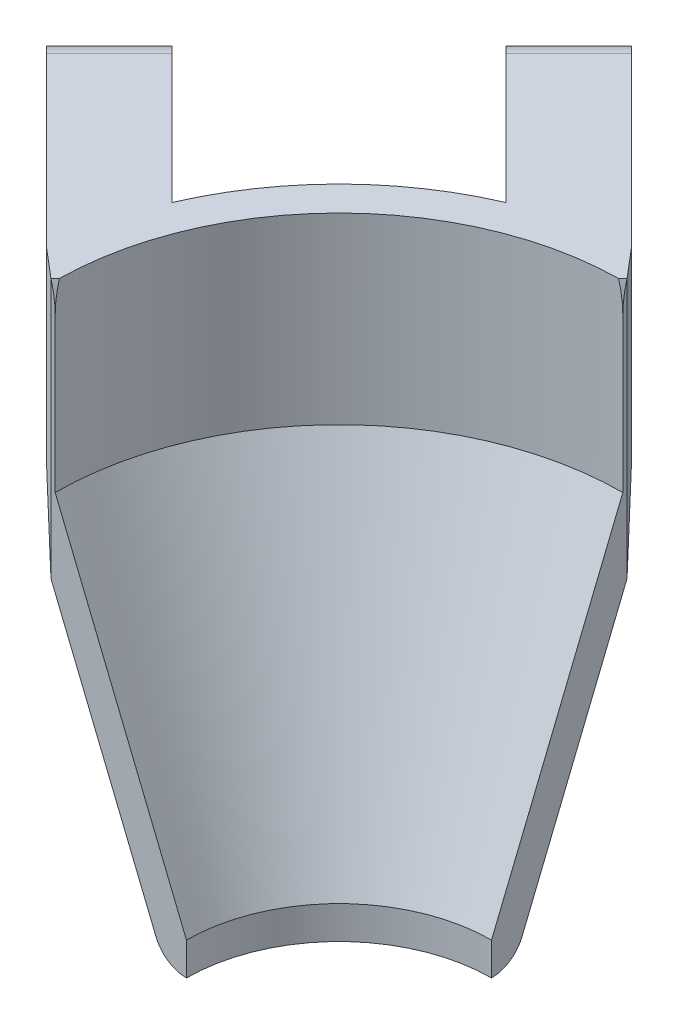
SolidWorks part; units mm, degrees
ref_plane "Alzado" through (0, 0, 0) normal (0, 0, 1) x (1, 0, 0)
ref_plane "Planta" through (0, 0, 0) normal (0, 1, 0) x (1, 0, 0)
ref_plane "Vista lateral" through (0, 0, 0) normal (1, 0, 0) x (0, 0, -1)
sketch "Croquis2" plane through (0, 0, 0) normal (1, 0, 0) x (0, 0, -1)
  line L0 (-25.7956, 35.8166) -> (-40.3139, 90) construction
  line L1 (-40.3139, 90) -> (-34.1023, 90) construction
  line L2 (-34.1023, 90) -> (-20, 37.3696) construction
  line L3 (0, 7.3696) -> (0, 0) construction
  line L4 (0, 0) -> (0, 65.5249) construction
  line L5 (34.1023, 90) -> (20, 37.3696) construction
  line L6 (40.3139, 90) -> (34.1023, 90) construction
  line L7 (25.7956, 35.8166) -> (40.3139, 90) construction
  arc A0 (0, 0) -> (-25.7956, 35.8166) centre (34.3409, 51.9302) cw construction
  arc A1 (-20, 37.3696) -> (0, 7.3696) centre (34.3409, 51.9302) ccw construction
  arc A2 (20, 37.3696) -> (0, 7.3696) centre (-34.3409, 51.9302) cw construction
  arc A3 (0, 0) -> (25.7956, 35.8166) centre (-34.3409, 51.9302) ccw construction
  dimension "D4" = 62.2578
  dimension "D5" = 90
  dimension "D1" = 15
  dimension "D2" = 20
  dimension "D3" = 6
sketch "Croquis3" plane through (0, 0, 0) normal (1, 0, 0) x (0, 0, -1)
  line L0 (25.7956, 0) -> (25.7956, 5.5557)
  line L1 (25.7956, 5.5557) -> (48, 60)
  line L2 (48, 60) -> (48, 91)
  line L3 (48, 91) -> (54, 91)
  line L4 (54, 91) -> (54, 60)
  line L5 (54, 60) -> (30.9399, 3.4577)
  line L6 (0, 0) -> (25.7956, 0) construction
  line L7 (25.7956, 0) -> (25.7956, 35.8166) construction
  line L8 (0, 0) -> (0, 65.5249) construction
  arc A0 (30.9399, 3.4577) -> (25.7956, 0) centre (25.7956, 5.5557) cw
  dimension "D1" = 48
  dimension "D2" = 6
  dimension "D3" = 91
  dimension "D4" = 60
revolve "Revolución1" add sketch "Croquis3" angle 90 about L4
sketch "Croquis4" plane through (0, 91, 0) normal (0, 1, 0) x (1, 0, 0)
  line L0 (0, 0) -> (-47.2208, 47.2208) construction
  line L1 (-85.5599, 36.0624) -> (-74.9533, 46.669)
  line L2 (-74.9533, 46.669) -> (-49.6104, 21.3262)
  line L3 (-53.8262, 4.3287) -> (-85.5599, 36.0624)
  line L4 (0, 0) -> (0, 25.7956) construction
  line L5 (-46.669, 74.9533) -> (-21.3262, 49.6104)
  line L6 (-36.0624, 85.5599) -> (-46.669, 74.9533)
  line L7 (-4.3287, 53.8262) -> (-36.0624, 85.5599)
  line L8 (-38.1838, 38.1838) -> (-66.0102, 10.3574) construction
  arc A0 (0, 54) -> (-54, 0) centre (0, 0) ccw construction
  arc A1 (-49.6104, 21.3262) -> (-53.8262, 4.3287) centre (0, 0) ccw
  arc A2 (-21.3262, 49.6104) -> (-4.3287, 53.8262) centre (0, 0) cw
  dimension "D1" = 45
  dimension "D2" = 15
  dimension "D3" = 20
  dimension "D4" = 32
extrude "Saliente-Extruir1" add sketch "Croquis4" against normal blind 10
fillet "Redondeo1" radius 6 2 edges at (-12.9995, 81, -52.412) (-52.412, 81, -12.9995)
sketch "Croquis5" plane through (-24.7487, 0, 24.7487) normal (-0.7071, 0, 0.7071) x (0.7071, 0, 0.7071)
  line L0 (-86, 81) -> (-86, 91) construction
  circle A0 centre (-59, 86) radius 3
  circle A1 centre (-78, 86) radius 3
  point P11 (-86, 86)
  dimension "D2" = 6
  dimension "D1" = 59
  dimension "D3" = 8
extrude "Cortar-Extruir1" cut sketch "Croquis5" against normal through all
fillet "Redondeo2" radius 5 4 edges at (-80.2566, 81, -41.3657) (-41.3657, 81, -80.2566) (-80.2566, 91, -41.3657) (-41.3657, 91, -80.2566)
ref_axis "Eje1" through (-7.3446, 86, -76.094) along (-0.7071, 0, 0.7071)
sketch "Croquis9" plane through (0, 91, 0) normal (0, 1, 0) x (1, 0, 0)
  line L0 (0, 0) -> (-41.7193, 41.7193) construction
  line L1 (-7.3446, 76.094) -> (-84.0335, -0.5949) construction
  line L2 (-53.8262, 4.3287) -> (-66.468, 16.9706) construction
  line L3 (-82.0244, 32.5269) -> (-53.8262, 4.3287) construction
  dimension "D1" = 59
  dimension "D2" = 17.8782
ref_plane "Plano2" through (27, 0, -27) normal (0.7071, 0, -0.7071) x (-0.7071, 0, -0.7071)
sketch "Croquis14" plane through (27, 0, -27) normal (0.7071, 0, -0.7071) x (-0.7071, 0, -0.7071)
  line L0 (59, 86) -> (33.9411, 86) construction
  line L1 (33.9411, 91) -> (33.9411, 60) construction
  line L2 (0, 91) -> (59, 91) construction
  line L3 (34.445, 91) -> (33.9411, 91)
  line L4 (33.9411, 91) -> (33.9411, 86)
  arc A0 (33.9411, 86) -> (34.445, 91) centre (59, 86) cw
extrude "Cortar-Extruir3" cut sketch "Croquis14" against normal through all
sketch "Croquis17" plane through (0, 91, 0) normal (0, 1, 0) x (1, 0, 0)
  line L0 (-4.3287, 53.8262) -> (0, 48.7126)
  line L1 (0, 48.7126) -> (0, 54)
  line L2 (39.0562, 14.9438) -> (14.9438, 39.0562) construction
  line L3 (0, 54) -> (0, 48.7126) construction
  line L5 (0, 0) -> (-41.7193, 41.7193) construction
  line L6 (-53.8262, 4.3287) -> (-48.7126, 0)
  line L7 (-48.7126, 0) -> (-54, 0)
  arc A0 (-4.3287, 53.8262) -> (0, 54) centre (0, 0) cw
  arc A1 (-21.3262, 49.6104) -> (-49.6104, 21.3262) centre (0, 0) ccw construction
  arc A2 (-53.8262, 4.3287) -> (-54, 0) centre (0, 0) ccw
extrude "Cortar-Extruir4" cut sketch "Croquis17" against normal through all
